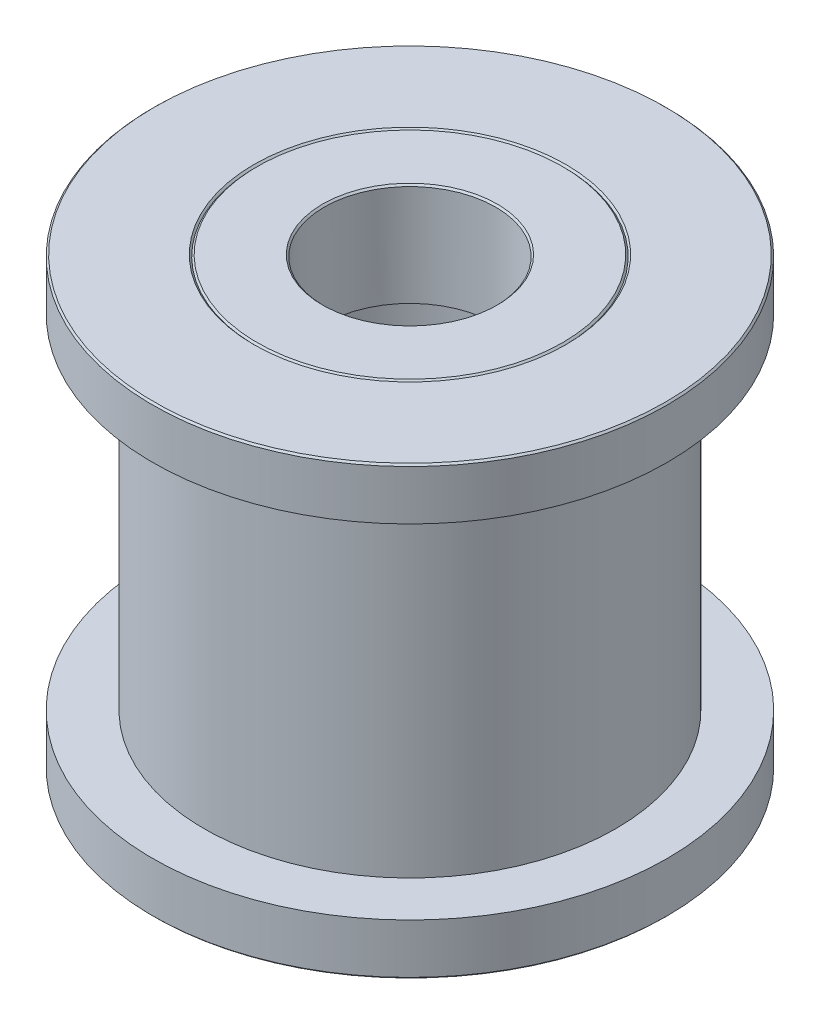
SolidWorks part; units mm, degrees
ref_plane "Front Plane" through (0, 0, 0) normal (0, 0, 1) x (1, 0, 0)
ref_plane "Top Plane" through (0, 0, 0) normal (0, 1, 0) x (1, 0, 0)
ref_plane "Right Plane" through (0, 0, 0) normal (1, 0, 0) x (0, 0, -1)
sketch "Sketch1" plane through (0, 0, 0) normal (0, 0, 1) x (1, 0, 0)
  line L0 (0, -12.8882) -> (0, 12.8882) construction
  line L1 (6, 2.9242) -> (7.5, 2.9242)
  line L5 (7.5, 4.4242) -> (7.5, 2.9242)
  line L9 (4.5, -8.5758) -> (4.5, -5.5758)
  line L16 (4.5, 4.4242) -> (7.5, 4.4242)
  line L17 (6, -7.0758) -> (6, 2.9242)
  line L18 (6, -7.0758) -> (7.5, -7.0758)
  line L19 (3.5, -5.5758) -> (3.5, 1.4242)
  line L22 (3.5, 1.4242) -> (4.5, 1.4242)
  line L23 (4.5, 4.4242) -> (4.5, 1.4242)
  line L24 (7.5, -7.0758) -> (7.5, -8.5758)
  line L25 (3.5, -5.5758) -> (4.5, -5.5758)
  line L26 (4.5, -8.5758) -> (7.5, -8.5758)
  line L28 (4.5, 1.4242) -> (2.5, 1.4242)
  line L29 (4.5, 1.4242) -> (4.5, 4.4242)
  line L30 (4.5, 4.4242) -> (2.5, 4.4242)
  line L31 (2.5, 1.4242) -> (2.5, 4.4242)
  line L32 (4.5, -5.5758) -> (2.5, -5.5758)
  line L33 (4.5, -5.5758) -> (4.5, -8.5758)
  line L34 (4.5, -8.5758) -> (2.5, -8.5758)
  line L35 (2.5, -5.5758) -> (2.5, -8.5758)
  point P4 (0, 0)
  dimension "D1" = 13
  dimension "D2" = 1.5
  dimension "D3" = 3
  dimension "D4" = 1.5
  dimension "D5" = 3.5
  dimension "D6" = 4.5
  dimension "D7" = 6
  dimension "D8" = 7.5
  dimension "D9" = 3
  dimension "D10" = 1
  dimension "D11" = 2
  dimension "D12" = 2
revolve "Revolve1" add sketch "Sketch1" angle 360 about L0 region at (5.1855, -2.0758, 0)
chamfer "Chamfer1" distance 0.05 angle 45 4 edges at (4.5, -8.5758, 0) (4.5, 4.4242, 0) (7.5, 4.4242, 0) (7.5, -8.5758, 0)
revolve "Revolve2" add sketch "Sketch1<3>" angle 360 about L0 region at (3.5, 2.9242, 0) region at (3.5, -7.0758, 0)
sketch "Sketch1<3>" plane through (0, 0, 0) normal (0, 0, 1) x (1, 0, 0) same geometry as "Sketch1"
chamfer "Chamfer2" distance 0.05 angle 45 2 edges at (4.5, -8.5758, 0) (2.5, -8.5758, 0)
chamfer "Chamfer3" distance 0.05 angle 45 2 edges at (4.5, 4.4242, 0) (2.5, 4.4242, 0)
